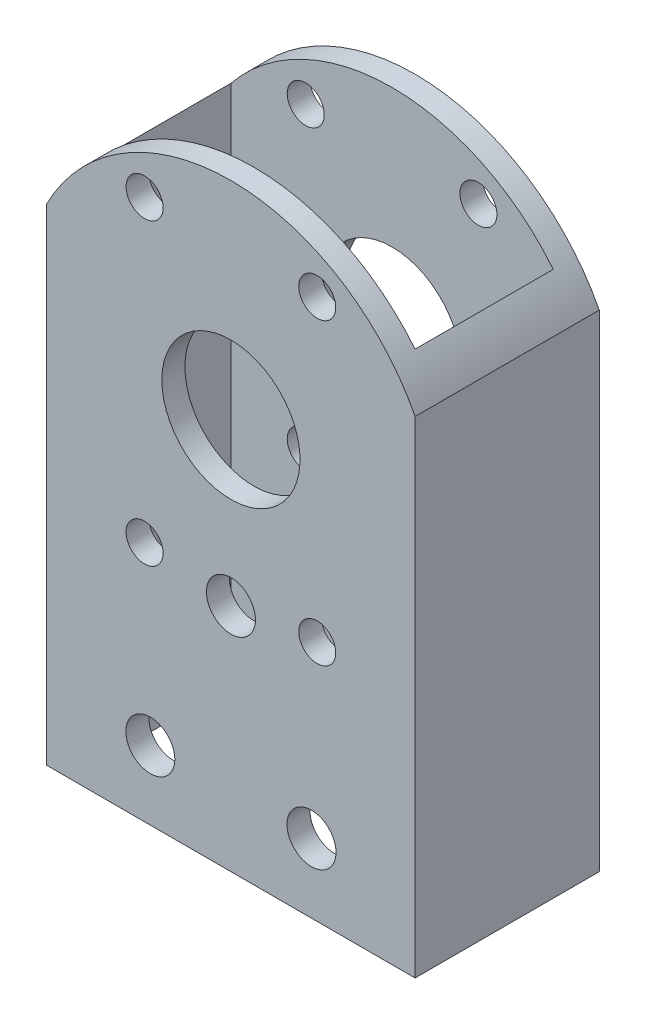
SolidWorks part; units mm, degrees
material "6061-T6 (SS)"
ref_plane "Front" through (0, 0, 0) normal (0, 0, 1) x (1, 0, 0)
ref_plane "Top" through (0, 0, 0) normal (0, 1, 0) x (1, 0, 0)
ref_plane "Right" through (0, 0, 0) normal (1, 0, 0) x (0, 0, -1)
sketch "Sketch1" plane through (0, 0, 0) normal (0, 1, 0) x (1, 0, 0)
  line L1 (-25.4, -12.7) -> (25.4, -12.7)
  line L2 (-25.4, -12.7) -> (-25.4, 12.7)
  line L3 (-25.4, 12.7) -> (25.4, 12.7)
  line L4 (25.4, -12.7) -> (25.4, 12.7)
  line L5 (-25.4, -12.7) -> (25.4, 12.7) construction
  line L6 (-25.4, 12.7) -> (25.4, -12.7) construction
  point P0 (0, 0)
  dimension "D1" = 25.4
  dimension "D2" = 50.8
extrude "Extrude-Thin1" add sketch "Sketch1" along normal blind 82.55 thin thin type one direction reverse wall 3.175
sketch "Sketch2" plane through (0, 0, -12.7) normal (0, 0, -1) x (-1, 0, 0)
  line L0 (0, 82.55) -> (0, 50.8)
  line L1 (-25.4, 82.55) -> (25.4, 82.55) construction
  line L3 (0, 41.275) -> (0, 60.325) construction
  circle A1 centre (0, 50.8) radius 23.8125
  circle A3 centre (0, 50.8) radius 9.525
  point P12 (0, 50.8)
  dimension "D1" = 19.05
  dimension "D3" = 47.625
  dimension "D2" = 31.75
hole_wizard "#10 Clearance Hole1" positions "Sketch5" profile "Sketch6" hole size "#10" standard "ANSI Inch" end condition through all
sketch "Sketch5" plane through (0, 0, -12.7) normal (0, 0, -1) x (-1, 0, 0)
  line L0 (0, 82.55) -> (0, 53.975)
  line L1 (-25.4, 82.55) -> (25.4, 82.55) construction
  line L3 (-11.9063, 74.5972) -> (11.9063, 74.5972)
  line L4 (-11.9063, 74.5972) -> (-11.9063, 33.3528)
  line L5 (-11.9063, 33.3528) -> (11.9063, 33.3528)
  line L6 (11.9063, 74.5972) -> (11.9063, 33.3528)
  circle A0 centre (0, 53.975) radius 23.8125
  point P21 (-11.9063, 74.5972)
  point P22 (11.9063, 74.5972)
  point P24 (11.9063, 33.3528)
  point P25 (-11.9063, 33.3528)
  dimension "D1" = 47.625
  dimension "D2" = 28.575
  dimension "D3" = 23.8125
sketch "Sketch6" plane through (11.9063, 33.3528, -12.7) normal (1, 0, 0) x (0, 1, 0)
  line L0 (0, 0) -> (0, 25.4)
  line L1 (0, 25.4) -> (2.5527, 25.4)
  line L2 (2.5527, 25.4) -> (2.5527, 0)
  line L5 (2.5527, 0) -> (0, 0)
  line L11 (0, -6.35) -> (0, 107.95) construction
  dimension "Thru Hole Dia." = 5.1054
  dimension "Thru Hole Depth" = 25.4
sketch "Sketch7" plane through (0, 0, -12.7) normal (0, 0, -1) x (-1, 0, 0)
  line L0 (-11.9063, 74.5972) -> (11.9063, 33.3528) construction
  circle A1 centre (0, 53.975) radius 9.525
  point P9 (0, 53.975)
  dimension "D1" = 19.05
extrude "Cut-Extrude2" cut sketch "Sketch7" against normal through all both
hole_wizard "1/4 Clearance Hole2" positions "Sketch8" profile "Sketch9" hole size "1/4" standard "ANSI Inch" end condition through all
sketch "Sketch8" plane through (0, 0, 12.7) normal (0, 0, 1) x (1, 0, 0)
  line L2 (-25.4, 82.55) -> (-25.4, 0) construction
  line L4 (-25.4, 0) -> (25.4, 0) construction
  point P0 (-11.1125, 9.525)
  point P2 (11.1125, 9.525)
  point P14 (-109.1715, 68.7854)
  dimension "D1" = 22.225
  dimension "D2" = 14.2875
  dimension "D3" = 9.525
sketch "Sketch9" plane through (-11.1125, 9.525, 12.7) normal (1, 0, 0) x (0, -1, 0)
  line L0 (0, 0) -> (0, 25.4)
  line L1 (0, 25.4) -> (3.3782, 25.4)
  line L2 (3.3782, 25.4) -> (3.3782, 0)
  line L5 (3.3782, 0) -> (0, 0)
  line L11 (0, -6.35) -> (0, 107.95) construction
  dimension "Thru Hole Dia." = 6.7564
  dimension "Thru Hole Depth" = 25.4
sketch "Sketch10" plane through (0, 0, -12.7) normal (0, 0, -1) x (-1, 0, 0)
  line L0 (-25.4, 67.0659) -> (-25.4, 82.55)
  line L1 (-25.4, 82.55) -> (25.4, 82.55)
  line L2 (25.4, 82.55) -> (25.4, 67.0659)
  line L3 (25.4, 82.55) -> (25.4, 0) construction
  arc A0 (25.4, 67.0659) -> (-25.4, 67.0659) centre (0, 53.975) ccw
  line M13 (25.4, 0) -> (25.4, 82.55)
  line M14 (25.4, 82.55) -> (-25.4, 82.55)
  line M15 (-25.4, 82.55) -> (-25.4, 0)
extrude "Cut-Extrude3" cut sketch "Sketch10" against normal through all contours A0 L1 M15 | A0 M13 M14 region at (-19.4433, 78.2444, -12.7) region at (19.4433, 78.2444, -12.7)
sketch "Sketch13" plane through (0, 0, 12.7) normal (0, 0, 1) x (1, 0, 0)
  line L4 (-25.4, 67.0659) -> (-25.4, 0) construction
  point P0 (0, 31.75)
  dimension "D1" = 31.75
  dimension "D2" = 25.4
hole_wizard "1/4 Clearance Hole1" positions "Sketch13" profile "Sketch12" hole size "1/4" standard "ANSI Inch" end condition through all
sketch "Sketch12" plane through (0, 31.75, 12.7) normal (1, 0, 0) x (0, -1, 0)
  line L0 (0, 0) -> (0, 25.4)
  line L1 (0, 25.4) -> (3.3782, 25.4)
  line L2 (3.3782, 25.4) -> (3.3782, 0)
  line L5 (3.3782, 0) -> (0, 0)
  line L11 (0, -6.35) -> (0, 107.95) construction
  dimension "Thru Hole Dia." = 6.7564
  dimension "Thru Hole Depth" = 25.4
